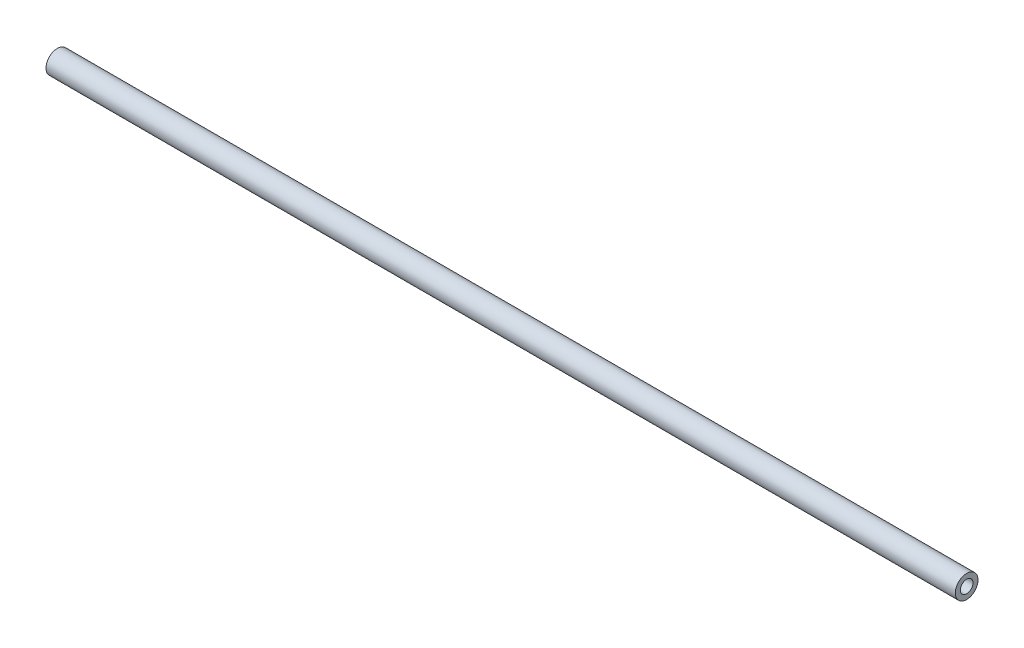
SolidWorks part; units mm, degrees
ref_plane "Front Plane" through (0, 0, 0) normal (0, 0, 1) x (1, 0, 0)
ref_plane "Top Plane" through (0, 0, 0) normal (0, 1, 0) x (1, 0, 0)
ref_plane "Right Plane" through (0, 0, 0) normal (1, 0, 0) x (0, 0, -1)
ref_axis "Axis1" through (-88.99, 0, 0) along (1, 0, 0)
sketch "Sketch1" plane through (0, 0, 0) normal (1, 0, 0) x (0, 0, -1)
  circle A0 centre (0, 0) radius 0.625
  circle A1 centre (0, 0) radius 1.125
  dimension "D1" = 1.25
  dimension "D2" = 0.5
extrude "Boss-Extrude1" add sketch "Sketch1" along normal blind 90
